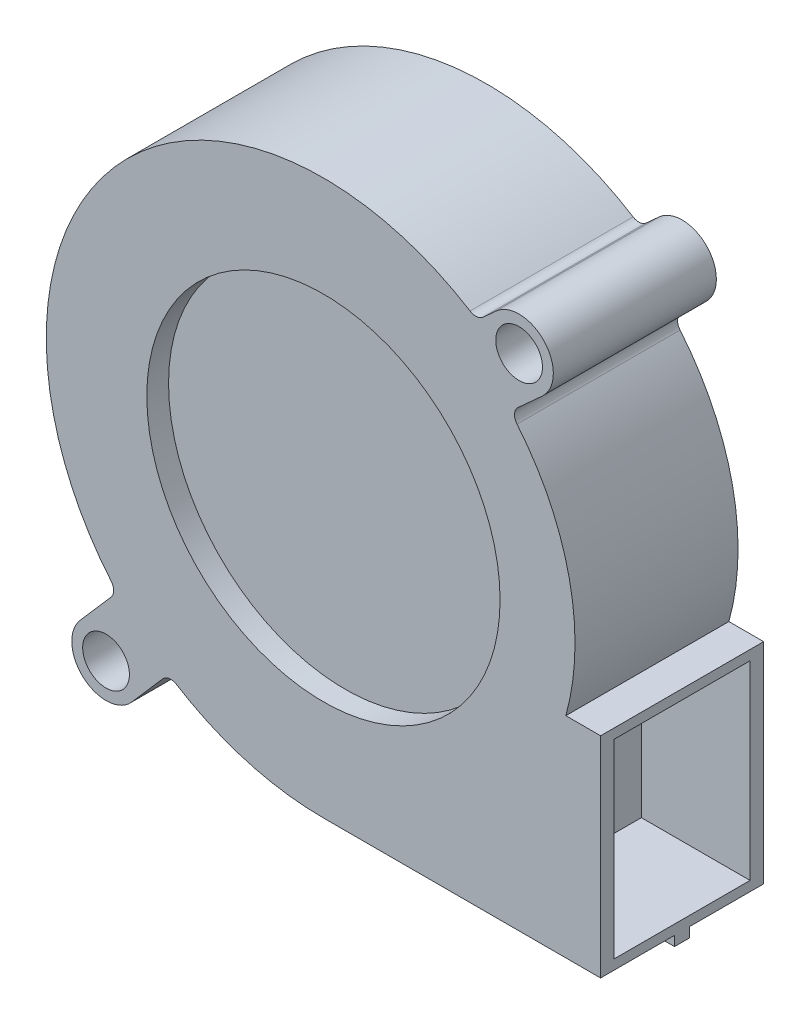
SolidWorks part; units mm, degrees
ref_plane "Front" through (0, 0, 0) normal (0, 0, 1) x (1, 0, 0)
ref_plane "Top" through (0, 0, 0) normal (0, 1, 0) x (1, 0, 0)
ref_plane "Right" through (0, 0, 0) normal (1, 0, 0) x (0, 0, -1)
sketch "Sketch1" plane through (0, 0, 0) normal (0, 0, 1) x (1, 0, 0)
  line L0 (0, 0) -> (-25.5, 0) construction
  line L1 (25.5, -25.5) -> (0, -25.5)
  line L2 (25.5, -25.5) -> (25.5, -6.2)
  line L3 (25.5, -6.2) -> (0, -6.2)
  line L4 (0, -25.5) -> (0, -6.2)
  line L5 (25.5, -25.5) -> (0, -6.2) construction
  line L6 (25.5, -6.2) -> (0, -25.5) construction
  line L7 (-17.623, -25.067) -> (-14.7972, -21.8173)
  line L8 (-14.2274, -21.162) -> (-18.9814, -17.0281) construction
  line L9 (-22.377, -20.933) -> (-19.5512, -17.6834)
  line L10 (15.8812, 22.8309) -> (14.6907, 21.7488)
  line L11 (14.1225, 21.2322) -> (18.9284, 17.087) construction
  line L12 (18.9284, 17.087) -> (20.1188, 18.1691)
  line L13 (18.9284, 17.087) -> (17.9083, 16.1597)
  arc A0 (-13.5127, -21.6254) -> (24.7348, -6.2) centre (0, 0) ccw
  circle A1 centre (18, 20.5) radius 2.15
  circle A2 centre (-20, -23) radius 2.15
  circle A3 centre (18, 20.5) radius 3.15
  circle A4 centre (-20, -23) radius 3.15
  arc A5 (-18.9814, -17.0281) -> (-14.2274, -21.162) centre (0, 0) ccw construction
  arc A6 (-14.7972, -21.8173) -> (-13.5127, -21.6254) centre (-14.0426, -22.4735) cw
  arc A7 (-19.5395, -16.3846) -> (-19.5512, -17.6834) centre (-20.3058, -17.0272) cw
  arc A8 (13.4891, 21.6401) -> (-19.5395, -16.3846) centre (0, 0) ccw
  arc A9 (14.858, 20.7241) -> (14.1225, 21.2322) centre (0, 0) ccw construction
  arc A10 (18.6286, 17.4134) -> (14.858, 20.7241) centre (0, 0) ccw construction
  arc A11 (18.9284, 17.087) -> (18.6286, 17.4134) centre (0, 0) ccw construction
  arc A12 (17.1864, 15.5035) -> (-23.1458, 0) centre (0, 0) ccw construction
  arc A13 (22.3, -6.2) -> (17.8115, 14.7811) centre (0, 0) ccw
  arc A14 (-23.1458, 0) -> (21.089, -9.5385) centre (0, 0) ccw construction
  arc A15 (21.089, -9.5385) -> (22.3, -6.2) centre (0, 0) ccw construction
  arc A16 (24.7348, -6.2) -> (18.9284, 17.087) centre (0, 0) ccw construction
  arc A17 (17.8115, 14.7811) -> (17.9083, 16.1597) centre (18.581, 15.4198) cw
  arc A18 (14.6907, 21.7488) -> (13.4891, 21.6401) centre (14.0181, 22.4887) cw
  point P7 (12.75, -15.85)
  point P29 (22.3, -6.2)
  dimension "D1" = 51
  dimension "D6" = 4.3
  dimension "D9" = 1
  dimension "D10" = 1
  dimension "D11" = 1
  dimension "D2" = 51
  dimension "D3" = 19.3
  dimension "D4" = 18
  dimension "D5" = 20.5
  dimension "D7" = 23
  dimension "D8" = 20
  dimension "D12" = 3.2
extrude "Boss-Extrude1" add sketch "Sketch1" along normal mid plane 15 contours L10 A8 A7 L9 A4 L7 A6 A0 L4 L3 L12 A3 | A4 A2 | A3 A1 | L4 A0 L3 | A0 L1 L2 L3 region at (19.7418, -19.9767, 0) region at (-3.1548, 2.634, 0) region at (10.0263, -14.2424, 0) region at (-22.0085, -25.3098, 0) region at (15.735, 18.4411, 0)
sketch "Sketch3" plane through (25.5, 0, 0) normal (1, 0, 0) x (0, 0, -1)
  line L0 (-7.5, -25.5) -> (7.5, -25.5) construction
  line L1 (-0.7, -25.5) -> (0.7, -25.5)
  line L2 (-0.7, -25.5) -> (-0.7, -26.4)
  line L3 (-0.7, -26.4) -> (0.7, -26.4)
  line L4 (0.7, -25.5) -> (0.7, -26.4)
  line L5 (-0.7, -25.5) -> (0.7, -26.4) construction
  line L6 (-0.7, -26.4) -> (0.7, -25.5) construction
  point P4 (0, -25.95)
  dimension "D1" = 0.9
  dimension "D2" = 1.4
extrude "Boss-Extrude2" add sketch "Sketch3" against normal blind 3
sketch "Sketch4" plane through (0, 0, 7.5) normal (0, 0, 1) x (1, 0, 0)
  circle A0 centre (0, 0) radius 16.25
  dimension "D1" = 32.5
extrude "Cut-Extrude1" cut sketch "Sketch4" against normal blind 2
sketch "Sketch5" plane through (25.5, 0, 0) normal (1, 0, 0) x (0, 0, -1)
  line L0 (-7.5, -25.5) -> (-7.5, -6.2) construction
  line L1 (-6.25, -7.1) -> (6.25, -7.1)
  line L2 (-6.25, -7.1) -> (-6.25, -24.6)
  line L3 (-6.25, -24.6) -> (6.25, -24.6)
  line L4 (6.25, -7.1) -> (6.25, -24.6)
  line L5 (-6.25, -7.1) -> (6.25, -24.6) construction
  line L6 (-6.25, -24.6) -> (6.25, -7.1) construction
  point P4 (0, -15.85)
  point P9 (-7.5, -15.85)
  dimension "D1" = 12.5
  dimension "D2" = 17.5
extrude "Cut-Extrude2" cut sketch "Sketch5" against normal blind 10
